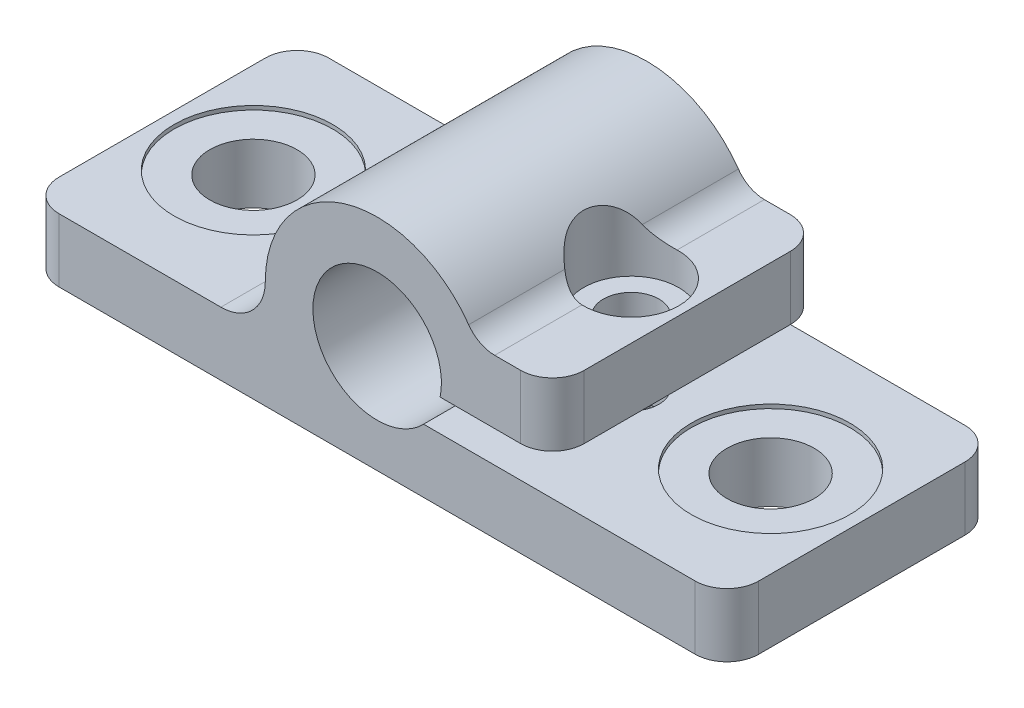
SolidWorks part; units mm, degrees
ref_plane "Front Plane" through (0, 0, 0) normal (0, 0, 1) x (1, 0, 0)
ref_plane "Top Plane" through (0, 0, 0) normal (0, 1, 0) x (1, 0, 0)
ref_plane "Right Plane" through (0, 0, 0) normal (1, 0, 0) x (0, 0, -1)
sketch "Sketch1" plane through (0, 0, 0) normal (0, 0, 1) x (1, 0, 0)
  line L0 (11.05, 4) -> (3.9702, 4)
  line L1 (-22.05, 2) -> (-9.85, 2)
  line L2 (-22.05, 2) -> (-22.05, -2)
  line L3 (-22.05, -2) -> (22.05, -2)
  line L4 (22.05, 2) -> (22.05, -2)
  line L5 (2.9262, 2) -> (22.05, 2)
  line L6 (6.2819, 8) -> (11.05, 8)
  line L7 (11.05, 8) -> (11.05, 4)
  line L9 (-7.95, 17.8613) -> (11.05, 17.8613) construction
  arc A0 (3.9702, 4) -> (2.9262, 2) centre (0, 4.8) ccw
  arc A2 (-7.05, 4.8) -> (-9.85, 2) centre (-9.85, 4.8) cw
  arc A4 (6.2819, 8) -> (-7.05, 4.8) centre (0, 4.8) ccw
  point P5 (-22.05, 0)
  point P27 (0, -2)
  dimension "D3" = 8.1
  dimension "D5" = 2.75
  dimension "D4" = 3
  dimension "D1" = 4
  dimension "D2" = 11
  dimension "D6" = 2
  dimension "D7" = 7
  dimension "D8" = 10
extrude "Boss-Extrude1" add sketch "Sketch1" along normal mid plane 17
sketch "Sketch2" plane through (0, 2, 0) normal (0, 1, 0) x (1, 0, 0)
  line L0 (0, 8.8123) -> (0, -8.5) construction
  line L1 (-7.05, -8.5) -> (6.2819, -8.5) construction
  line L2 (22.05, -8.5) -> (22.05, 8.5) construction
  circle A0 centre (16.3, 0) radius 2.75
  circle A1 centre (-16.3, 0) radius 2.75
  circle A2 centre (16.3, 0) radius 5
  circle A3 centre (-16.3, 0) radius 5
  dimension "D1" = 5.5
  dimension "D2" = 10
  dimension "D3" = 5.75
extrude "Cut-Extrude1" cut sketch "Sketch2" against normal through all and the other way up to surface (2 mm away) contours A0 | A1 region at (16.3, 2, 0) region at (-16.3, 2, 0) other way up to face at (7.5101, 4, 0)
extrude "Cut-Extrude2" cut sketch "Sketch2<3>" against normal offset from surface 3.75 and the other way up to surface (2 mm away) up to face at (0, -2, 0) other way up to face at (7.5101, 4, 0)
sketch "Sketch2<3>" plane through (0, 2, 0) normal (0, 1, 0) x (1, 0, 0) same geometry as "Sketch2"
ref_plane "Plane1" through (0, 11.85, 0) normal (0, 1, 0) x (1, 0, 0)
sketch "Sketch3" plane through (0, 11.85, 0) normal (0, 1, 0) x (1, 0, 0)
  line L0 (3.9702, 8.5) -> (11.05, 8.5) construction
  circle A0 centre (7.5101, 0) radius 3
  circle A1 centre (7.5101, 0) radius 1.75
  point P5 (7.5101, 8.5)
  dimension "D1" = 6
  dimension "D2" = 3.5
extrude "Cut-Extrude3" cut sketch "Sketch3" against normal through all contours A1 region at (7.5101, 11.85, 0)
extrude "Cut-Extrude4" cut sketch "Sketch3<3>" against normal offset from surface (5.85 mm away) 2 contours A1 | A0 A1 region at (4.595, 11.85, 0) region at (7.5101, 11.85, 0) up to face at (8.3676, 8, 0) offset beyond the face yes
sketch "Sketch3<3>" plane through (0, 11.85, 0) normal (0, 1, 0) x (1, 0, 0) same geometry as "Sketch3"
fillet "Fillet1" radius 2 4 edges at (22.05, 0, -8.5) (22.05, 0, 8.5) (-22.05, 0, -8.5) (-22.05, 0, 8.5)
fillet "Fillet2" radius 2 4 edges at (11.05, 6, -8.5) (11.05, 6, 8.5) (6.2819, 8, 5.6185) (6.2819, 8, -5.6185)
sketch "Sketch4" plane through (0, -2, 0) normal (0, -1, 0) x (1, 0, 0)
  line L1 (10.7721, 0) -> (9.1411, 2.825)
  line L2 (9.1411, 2.825) -> (5.8791, 2.825)
  line L3 (5.8791, 2.825) -> (4.2481, 0)
  line L4 (4.2481, 0) -> (5.8791, -2.825)
  line L5 (5.8791, -2.825) -> (9.1411, -2.825)
  line L6 (9.1411, -2.825) -> (10.7721, 0)
  circle A0 centre (7.5101, 0) radius 2.825 construction
  dimension "D1" = 5.65
extrude "Cut-Extrude5" cut sketch "Sketch4" against normal blind 2
